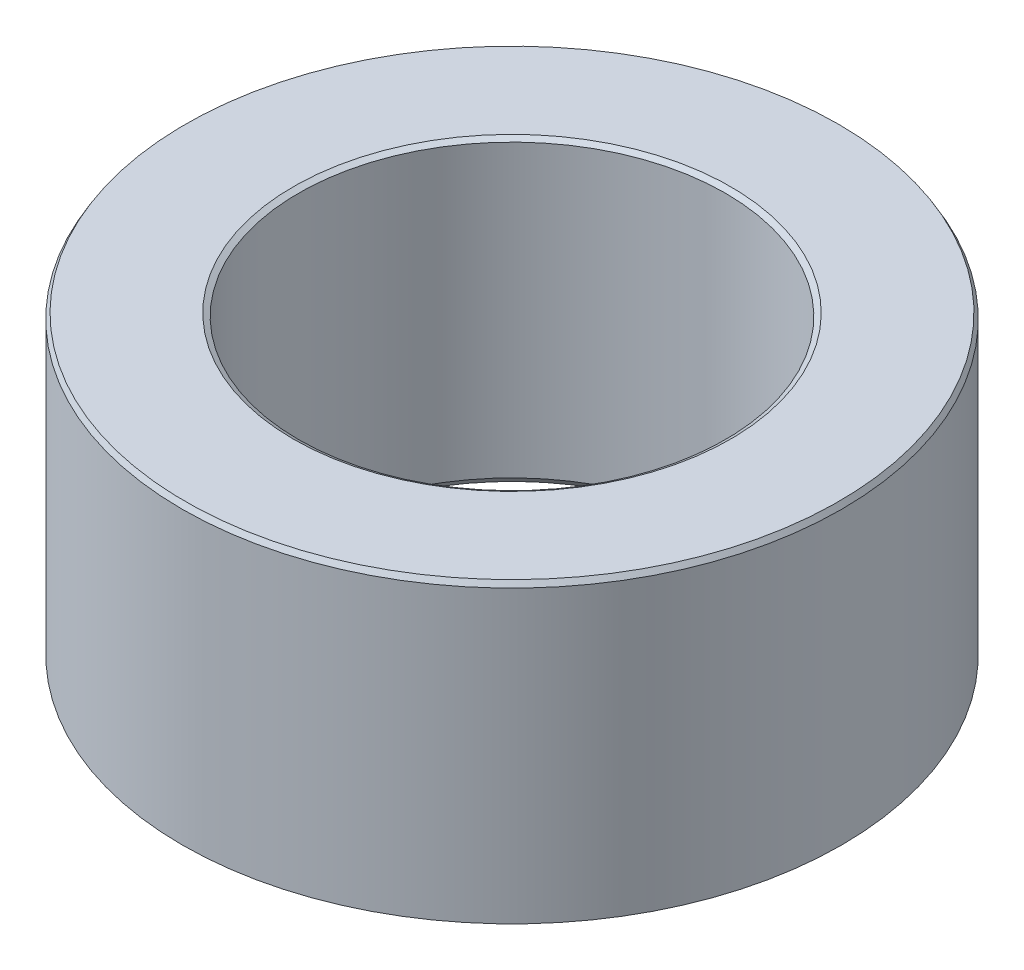
SolidWorks part; units mm, degrees
ref_plane "Front Plane" through (0, 0, 0) normal (0, 0, 1) x (1, 0, 0)
ref_plane "Top Plane" through (0, 0, 0) normal (0, 1, 0) x (1, 0, 0)
ref_plane "Right Plane" through (0, 0, 0) normal (1, 0, 0) x (0, 0, -1)
sketch "Sketch1" plane through (0, 0, 0) normal (0, 1, 0) x (1, 0, 0)
  circle A0 centre (0, 0) radius 45
  dimension "SLEEVE_OD" = 90
extrude "Boss-Extrude1" add sketch "Sketch1" along normal blind 40.8146
sketch "Sketch2" plane through (0, 0, 0) normal (0, 1, 0) x (1, 0, 0)
  circle A0 centre (0, 0) radius 29.1317
  dimension "BORE_D" = 58.2633
extrude "Cut-Extrude1" cut sketch "Sketch2" along normal through all
chamfer "Chamfer1" distance 0.7128 angle 30 4 edges at (0, 40.8146, 29.1317) (0, 0, 29.1317) (0, 0, 45) (0, 40.8146, 45) first distance on face at (0, 40.8146, 29.1317) first distance on face at (0, 0, 29.1317) first distance on face at (0, 40.8146, 45)
